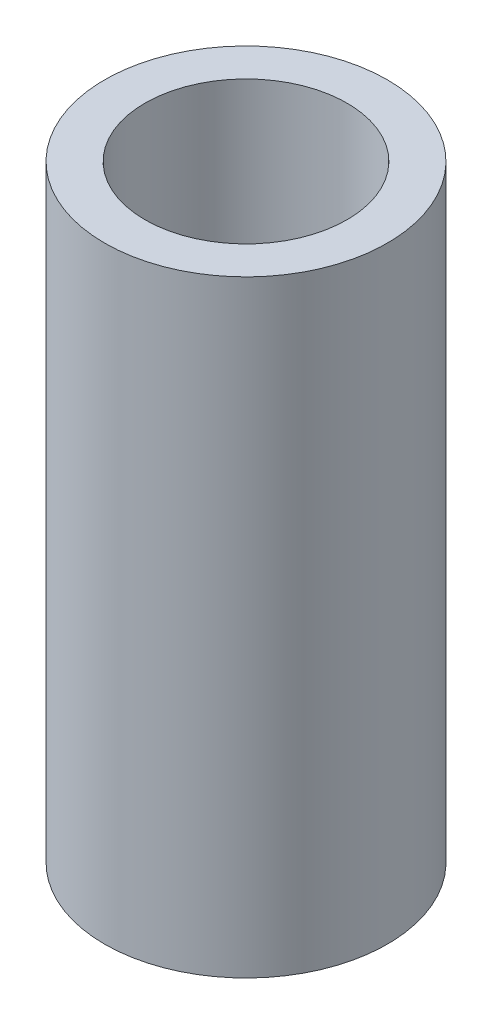
SolidWorks part; units mm, degrees
ref_plane "Front Plane" through (0, 0, 0) normal (0, 0, 1) x (1, 0, 0)
ref_plane "Top Plane" through (0, 0, 0) normal (0, 1, 0) x (1, 0, 0)
ref_plane "Right Plane" through (0, 0, 0) normal (1, 0, 0) x (0, 0, -1)
sketch "Sketch1" plane through (0, 0, 0) normal (0, 1, 0) x (1, 0, 0)
  circle A0 centre (0, 0) radius 17.5
  dimension "SLEEVE_OD" = 35
extrude "Boss-Extrude1" add sketch "Sketch1" along normal blind 75.139
sketch "Sketch2" plane through (0, 0, 0) normal (0, 1, 0) x (1, 0, 0)
  circle A0 centre (0, 0) radius 12.506
  dimension "BORE_D" = 25.0121
extrude "Cut-Extrude1" cut sketch "Sketch2" along normal through all
chamfer "Chamfer1" distance 2.7995 angle 45 rebuild error yes
